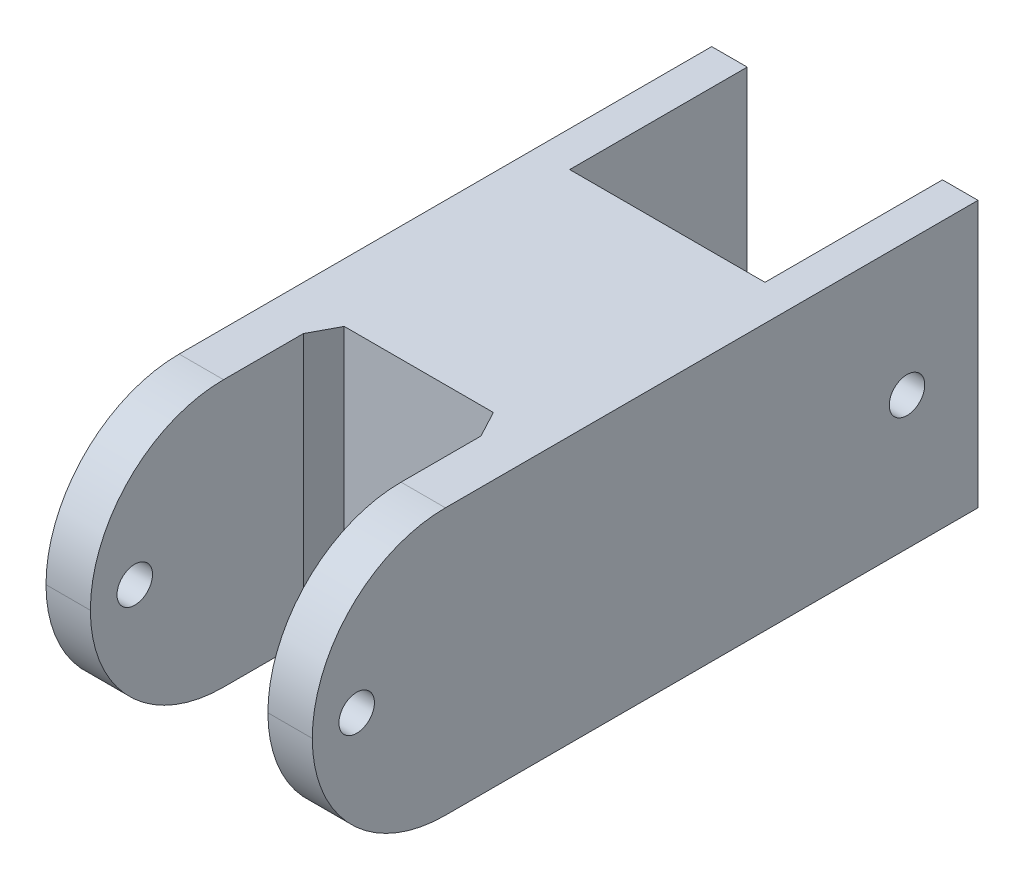
SolidWorks part; units mm, degrees
ref_plane "Front Plane" through (0, 0, 0) normal (0, 0, 1) x (1, 0, 0)
ref_plane "Top Plane" through (0, 0, 0) normal (0, 1, 0) x (1, 0, 0)
ref_plane "Right Plane" through (0, 0, 0) normal (1, 0, 0) x (0, 0, -1)
sketch "Sketch1" plane through (0, 0, 0) normal (0, 1, 0) x (1, 0, 0)
  line L1 (0, 0) -> (38.1, 0)
  line L2 (0, 0) -> (0, 38.1)
  line L3 (0, 38.1) -> (38.1, 38.1)
  line L4 (38.1, 0) -> (38.1, 38.1)
  dimension "D1" = 38.1
  dimension "D2" = 38.1
extrude "Prong holders" add sketch "Sketch1" along normal mid plane 38.1
sketch "Sketch4" plane through (0, 0, 0) normal (0, 1, 0) x (1, 0, 0)
  line L7 (31.75, 24.13) -> (29.718, 27.94)
  line L8 (29.718, 27.94) -> (8.382, 27.94)
  line L9 (8.382, 27.94) -> (6.35, 24.13)
  line L12 (19.05, 38.1) -> (19.05, 0) construction
  line L13 (38.1, 38.1) -> (0, 38.1) construction
  line L14 (0, 0) -> (38.1, 0) construction
  line L15 (31.75, 0) -> (6.35, 0)
  line L16 (31.75, 0) -> (31.75, 24.13)
  line L17 (6.35, 0) -> (6.35, 24.13)
  point P10 (27.2601, 20.32)
  point P15 (19.05, 0)
  point P16 (10.8789, 20.32)
  dimension "D1" = 2.032
  dimension "D2" = 3.81
  dimension "D3" = 2.032
  dimension "D4" = 25.4
  dimension "D5" = 27.94
sketch "Sketch5" plane through (38.1, 0, 0) normal (1, 0, 0) x (0, 0, -1)
  line L0 (0, 19.05) -> (0, -19.05) construction
  circle A0 centre (0, 0) radius 2.54
  dimension "D1" = 5.08
extrude "Screw holder" cut sketch "Sketch5" against normal through all
extrude "Groove cut out" cut sketch "Sketch4" against normal through all both and the other way through all
mirror "Mirror2" about plane through (0, 19.05, 0) normal (0, 0, -1) of "Prong holders", "Screw holder", "Groove cut out"
sketch "Sketch6" plane through (0, -19.05, 0) normal (0, -1, 0) x (1, 0, 0)
  line L0 (38.1, 38.1) -> (38.1, -38.1) construction
  line L1 (0, 38.1) -> (38.1, 38.1)
  line L2 (0, 38.1) -> (0, 6.35)
  line L3 (0, 6.35) -> (38.1, 6.35)
  line L4 (38.1, 38.1) -> (38.1, 6.35)
  dimension "D1" = 31.75
extrude "Opening of the top" cut sketch "Sketch6" against normal through all
fillet "Rounding off hoder edges" radius 19.05 4 edges at (3.175, -19.05, 6.35) (3.175, 19.05, 6.35) (34.925, 19.05, 6.35) (34.925, -19.05, 6.35)
sketch "Sketch7" plane through (0, 0, -38.1) normal (0, 0, -1) x (-1, 0, 0)
  line L4 (-38.1, -19.05) -> (0, -19.05)
  line L5 (0, -19.05) -> (0, 19.05)
  line L6 (0, 19.05) -> (-38.1, 19.05)
  line L7 (-38.1, 19.05) -> (-38.1, -19.05)
  line L8 (-38.1, -19.05) -> (0, -19.05)
  line L9 (0, -19.05) -> (0, 19.05)
  line L10 (0, 19.05) -> (-38.1, 19.05)
  line L11 (-38.1, 19.05) -> (-38.1, -19.05)
  dimension "D1" = 0
extrude "Adjustable length" add sketch "Sketch7" along normal blind 25.4
sketch "Sketch8" plane through (0, 0, -63.5) normal (0, 0, -1) x (-1, 0, 0)
  line L0 (-38.1, -19.05) -> (0, -19.05) construction
  line L1 (-38.1, 19.05) -> (-33.02, 19.05)
  line L2 (-38.1, 19.05) -> (-38.1, -19.05)
  line L3 (-38.1, -19.05) -> (-33.02, -19.05)
  line L4 (-33.02, 19.05) -> (-33.02, -19.05)
  line L6 (0, 19.05) -> (-5.08, 19.05)
  line L7 (0, 19.05) -> (0, -19.05)
  line L8 (0, -19.05) -> (-5.08, -19.05)
  line L9 (-5.08, 19.05) -> (-5.08, -19.05)
  dimension "D1" = 27.94
  dimension "D2" = 5.08
extrude "Boss-Extrude3" add sketch "Sketch8" along normal blind 25.4
sketch "Sketch9" plane through (38.1, 0, 0) normal (1, 0, 0) x (0, 0, -1)
  line L0 (78.74, 19.05) -> (78.74, -19.05) construction
  line L1 (12.7, 19.05) -> (88.9, 19.05) construction
  line L2 (12.7, -19.05) -> (88.9, -19.05) construction
  line L3 (78.74, 0) -> (88.9, 0) construction
  line L4 (88.9, 19.05) -> (88.9, -19.05) construction
  circle A0 centre (78.74, 0) radius 2.54
  dimension "D1" = 5.08
  dimension "D2" = 10.16
extrude "Cut-Extrude4" cut sketch "Sketch9" against normal through all
